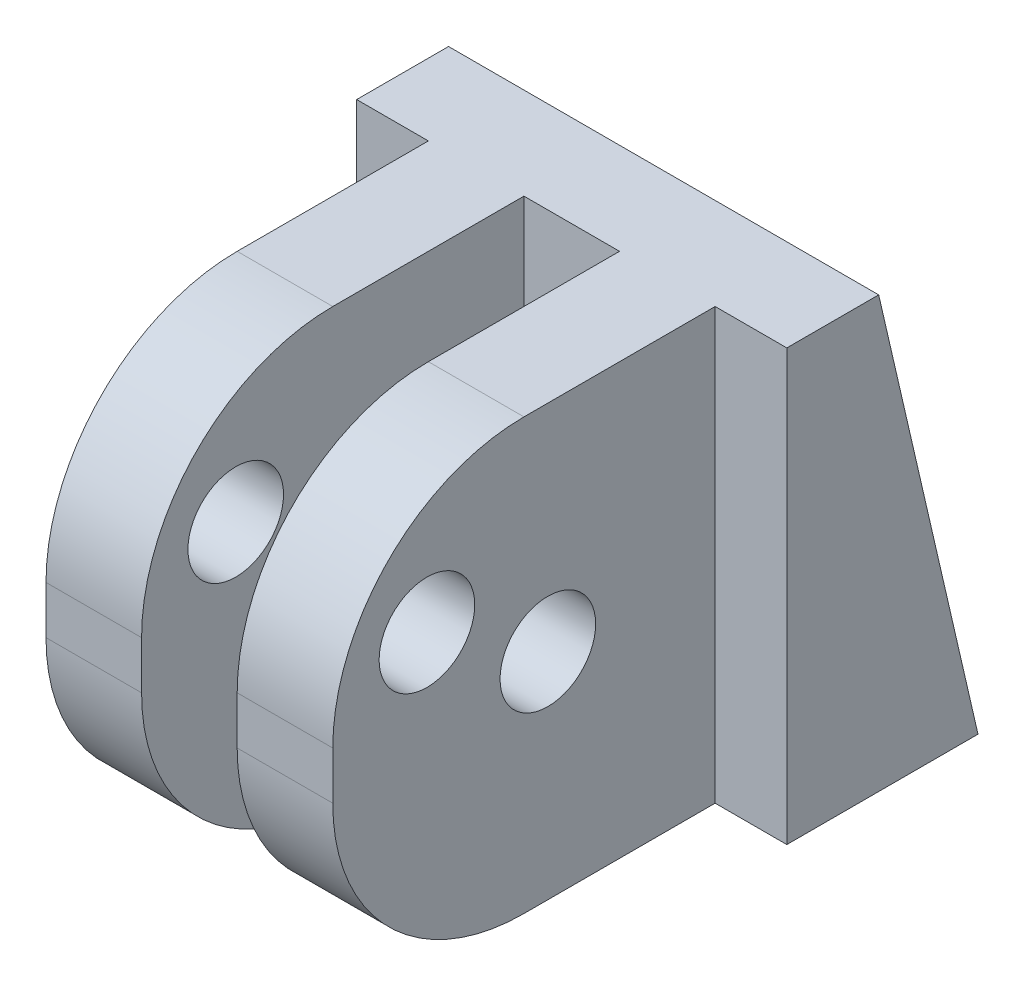
SolidWorks part; units mm, degrees
material "6061-T6 (SS)"
ref_plane "Front Plane" through (0, 0, 0) normal (0, 0, 1) x (1, 0, 0)
ref_plane "Top Plane" through (0, 0, 0) normal (0, 1, 0) x (1, 0, 0)
ref_plane "Right Plane" through (0, 0, 0) normal (1, 0, 0) x (0, 0, -1)
sketch "Sketch1" plane through (0, 0, 0) normal (0, 0, 1) x (1, 0, 0)
  line L1 (0, 0) -> (45, 0)
  line L2 (0, 0) -> (0, 45)
  line L3 (0, 45) -> (45, 45)
  line L4 (45, 0) -> (45, 45)
extrude "Boss-Extrude1" add sketch "Sketch1" along normal blind 20
sketch "Sketch2" plane through (0, 0, 20) normal (0, 0, 1) x (1, 0, 0)
  line L0 (45, 45) -> (0, 45) construction
  line L1 (7.5, 45) -> (17.5, 45)
  line L2 (7.5, 45) -> (7.5, 0)
  line L3 (7.5, 0) -> (17.5, 0)
  line L4 (17.5, 45) -> (17.5, 0)
  line L5 (0, 0) -> (45, 0) construction
  line L6 (0, 45) -> (0, 0) construction
  line L7 (27.5, 45) -> (37.5, 45)
  line L8 (27.5, 45) -> (27.5, 0)
  line L9 (27.5, 0) -> (37.5, 0)
  line L10 (37.5, 45) -> (37.5, 0)
  dimension "D1" = 7.5
  dimension "D2" = 10
  dimension "D3" = 10
  dimension "D4" = 10
extrude "Boss-Extrude2" add sketch "Sketch2" along normal blind 40
fillet "Fillet1" radius 20 4 edges at (32.5, 0, 60) (12.5, 0, 60) (32.5, 45, 60) (12.5, 45, 60)
sketch "Sketch3" plane through (0, 0, 0) normal (1, 0, 0) x (0, 0, -1)
  line L0 (0, 0) -> (-10.3891, 45)
  line L1 (-20, 45) -> (0, 45) construction
  line L2 (-10.3891, 45) -> (0, 45)
  line L3 (0, 45) -> (0, 0)
  dimension "D1" = 13
extrude "Cut-Extrude3" cut sketch "Sketch3" along normal through all
sketch "Sketch4" plane through (37.5, 0, 0) normal (1, 0, 0) x (0, 0, -1)
  line L5 (-40, 0) -> (-20, 0) construction
  line L6 (-60, 20) -> (-60, 25) construction
  line L7 (-50.1509, 30.5595) -> (-37.5, 22.5) construction
  line L8 (-37.5, 22.5) -> (-65.6527, 22.5) construction
  circle A1 centre (-50.1509, 30.5595) radius 5
  circle A2 centre (-37.5, 22.5) radius 5
  dimension "D1" = 32.5
  dimension "D3" = 10
  dimension "D4" = 10
  dimension "D2" = 15
  dimension "D5" = 22.5
  dimension "D6" = 22.5
extrude "Cut-Extrude4" cut sketch "Sketch4" against normal through all and the other way through all
sketch "Sketch5" plane through (0, 0, 0) normal (0, 0.225, -0.9744) x (-1, 0, 0)
  line L1 (-45, 46.1837) -> (-45, 0) construction
  line L2 (-22.5, 7.8971) -> (-22.5, 39.3821) construction
  line L3 (-45, 46.1837) -> (0, 46.1837) construction
  circle A1 centre (-22.5, 16.1837) radius 5
  circle A2 centre (-22.5, 36.1837) radius 5
  dimension "D1" = 10
  dimension "D2" = 10
  dimension "D3" = 10
  dimension "D4" = 20
  dimension "D5" = 22.5
extrude "Cut-Extrude5" cut sketch "Sketch5" against normal up to next
thread "Thread2" pitch 1.5 method extrude profile "Thread Profile4" start angle 0, offset 0, length 15, pitch 1.5, diameter 10
ref_plane "Plane4" through (27.5, 15.7689, 3.6405) normal (0, -0.9744, -0.225) x (1, 0, 0)
sketch "Thread Profile4" plane through (27.5, 15.7689, 3.6405) normal (0, -0.9744, -0.225) x (1, 0, 0)
  line L0 (0, 0) -> (0, 1.5) construction
  line L11 (0, 0) -> (0, 1.3125)
  line L12 (0, 1.3125) -> (-0.8119, 0.8437)
  line L13 (-0.8119, 0.8437) -> (-0.8119, 0.4687)
  line L15 (-0.8119, 0.4687) -> (0, 0)
  line L17 (-0.8119, 0.6562) -> (0, 0.6562) construction
  point P2 (0, 0)
  dimension "Pitch" = 1.5
  dimension "Profile_Angle" = 60
  dimension "Profile_Land" = 0.375
  dimension "Profile_Height" = 0.8119
thread "Thread3" pitch 1.5 method extrude profile "Thread Profile5" start angle 0, offset 0, length 10, pitch 1.5, diameter 10
ref_plane "Plane5" through (27.5, 35.2563, 8.1396) normal (0, -0.9744, -0.225) x (1, 0, 0)
sketch "Thread Profile5" plane through (27.5, 35.2563, 8.1396) normal (0, -0.9744, -0.225) x (1, 0, 0)
  line L0 (0, 0) -> (0, 1.5) construction
  line L11 (0, 0) -> (0, 1.3125)
  line L12 (0, 1.3125) -> (-0.8119, 0.8437)
  line L13 (-0.8119, 0.8437) -> (-0.8119, 0.4687)
  line L15 (-0.8119, 0.4687) -> (0, 0)
  line L17 (-0.8119, 0.6562) -> (0, 0.6562) construction
  point P2 (0, 0)
  dimension "Pitch" = 1.5
  dimension "Profile_Angle" = 60
  dimension "Profile_Land" = 0.375
  dimension "Profile_Height" = 0.8119
